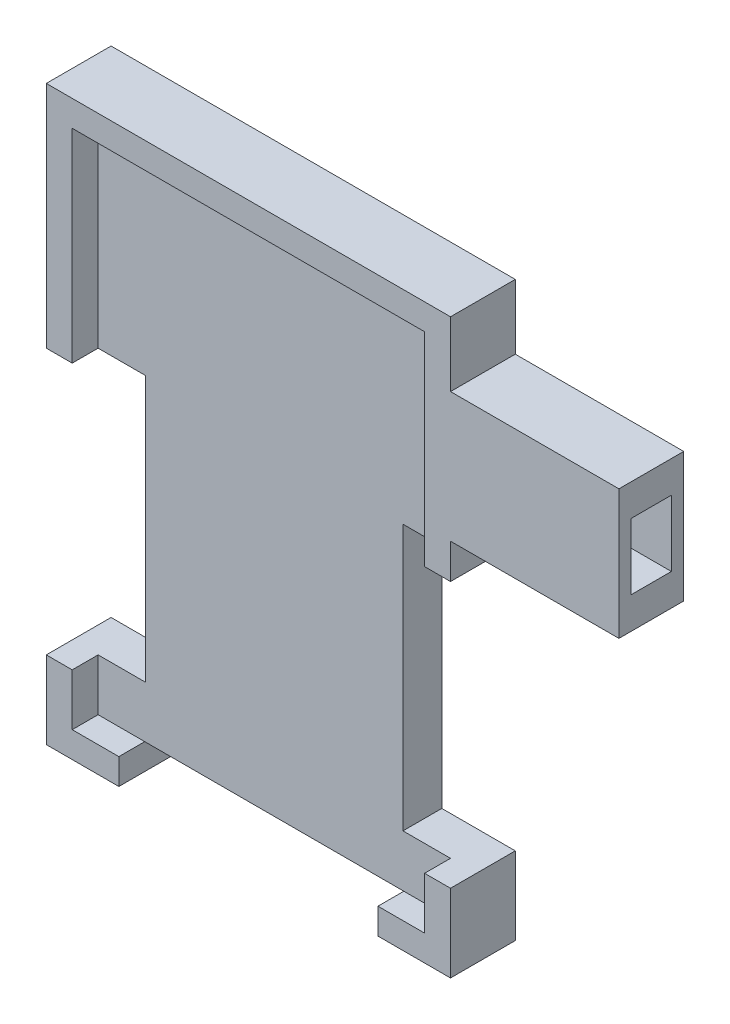
SolidWorks part; units mm, degrees
ref_plane "Front Plane" through (0, 0, 0) normal (0, 0, 1) x (1, 0, 0)
ref_plane "Top Plane" through (0, 0, 0) normal (0, 1, 0) x (1, 0, 0)
ref_plane "Right Plane" through (0, 0, 0) normal (1, 0, 0) x (0, 0, -1)
sketch "Sketch1" plane through (0, 0, 0) normal (0, 0, 1) x (1, 0, 0)
  line L0 (0, 125.6426) -> (0, -121.4419) construction
  line L1 (115.8733, 0) -> (-115.4548, 0) construction
  line L2 (15.6, 17.1) -> (28.6, 17.1)
  line L3 (-13.6, 20.1) -> (13.6, 20.1)
  line L4 (-13.6, 20.1) -> (-13.6, -20.1)
  line L5 (-13.6, -20.1) -> (13.6, -20.1)
  line L6 (13.6, 20.1) -> (13.6, -20.1)
  line L7 (-15.6, 22.1) -> (15.6, 22.1)
  line L8 (-15.6, 22.1) -> (-15.6, -22.1)
  line L9 (-15.6, -22.1) -> (15.6, -22.1)
  line L10 (15.6, 22.1) -> (15.6, -22.1)
  line L11 (28.6, 17.1) -> (28.6, 7.1)
  line L12 (28.6, 7.1) -> (15.6, 7.1)
  line L13 (11.43, 34.3394) -> (11.43, -39.7508) construction
  line L18 (-11.43, 31.8587) -> (-11.43, -35.1753) construction
  line L19 (-35.462, -16.1) -> (38.077, -16.1) construction
  line L20 (-9.93, -16.1) -> (-20.8868, -16.1)
  line L21 (9.93, 4.4) -> (20.8868, 4.4)
  line L22 (9.93, 4.4) -> (9.93, -16.1)
  line L23 (9.93, -16.1) -> (20.8868, -16.1)
  line L24 (20.8868, 4.4) -> (20.8868, -16.1)
  line L25 (-20.8868, 4.4) -> (-20.8868, -16.1)
  line L26 (-9.93, 4.4) -> (-20.8868, 4.4)
  line L27 (-9.93, 4.4) -> (-9.93, -16.1)
  line L28 (-10, -20.1) -> (-10, -22.1)
  line L29 (10, -20.1) -> (10, -22.1)
  line L30 (-35.1462, 12.1) -> (46.8082, 12.1) construction
  dimension "D1" = 31.2
  dimension "D2" = 2
  dimension "D3" = 27.2
  dimension "D4" = 40.2
  dimension "D5" = 22.86
  dimension "D6" = 4
  dimension "D7" = 1.5
  dimension "D8" = 20.5
  dimension "D9" = 10
  dimension "D10" = 10
  dimension "D11" = 5
  dimension "D12" = 13
  dimension "D13" = 28.6
  dimension "D14" = 28.2
extrude "Boss-Extrude1" add sketch "Sketch1" along normal blind 3 contours L26 L27 L20 L4 L5 L6 L23 L22 L21 L3 region at (0, 0.9335, 0)
extrude "Boss-Extrude2" add sketch "Sketch1<3>" along normal blind 5 contours L26 L4 L3 L6 L21 L10 L7 L8 | L5 L29 L9 L10 L23 L6 | L28 L5 L4 L20 L8 L9 region at (15.2413, 12.1, 0) region at (15.5179, -19.1, 0) region at (-14.6, -16.1821, 0)
sketch "Sketch1<3>" plane through (0, 0, 0) normal (0, 0, 1) x (1, 0, 0) same geometry as "Sketch1"
extrude "Boss-Extrude3" add sketch "Sketch1<4>" along normal blind 5 contours L12 L11 L2 L10 region at (22.1, 12.1, 0)
sketch "Sketch1<4>" plane through (0, 0, 0) normal (0, 0, 1) x (1, 0, 0) same geometry as "Sketch1"
sketch "Sketch2" plane through (28.6, 0, 0) normal (1, 0, 0) x (0, 0, -1)
  line L0 (0, 29.5595) -> (0, -33.1158) construction
  line L1 (-8.6556, 17.1) -> (3.1924, 17.1) construction
  line L2 (-5, 17.1) -> (0, 17.1) construction
  line L3 (-9.4008, 7.1) -> (5.047, 7.1) construction
  line L4 (-5, 7.1) -> (0, 7.1) construction
  line L5 (-2.5, 17.4146) -> (-2.5, 3.5219) construction
  line L6 (-7.7956, 12.1) -> (3.8426, 12.1) construction
  line L8 (-4.05, 14.65) -> (-0.95, 14.65)
  line L9 (-4.05, 14.65) -> (-4.05, 9.55)
  line L10 (-4.05, 9.55) -> (-0.95, 9.55)
  line L11 (-0.95, 14.65) -> (-0.95, 9.55)
  dimension "D1" = 2.5
  dimension "D2" = 5
  dimension "D3" = 5
  dimension "D4" = 3.1
  dimension "D5" = 5.1
extrude "Cut-Extrude1" cut sketch "Sketch2" against normal blind 6 contours L9 L8 L11 L10
